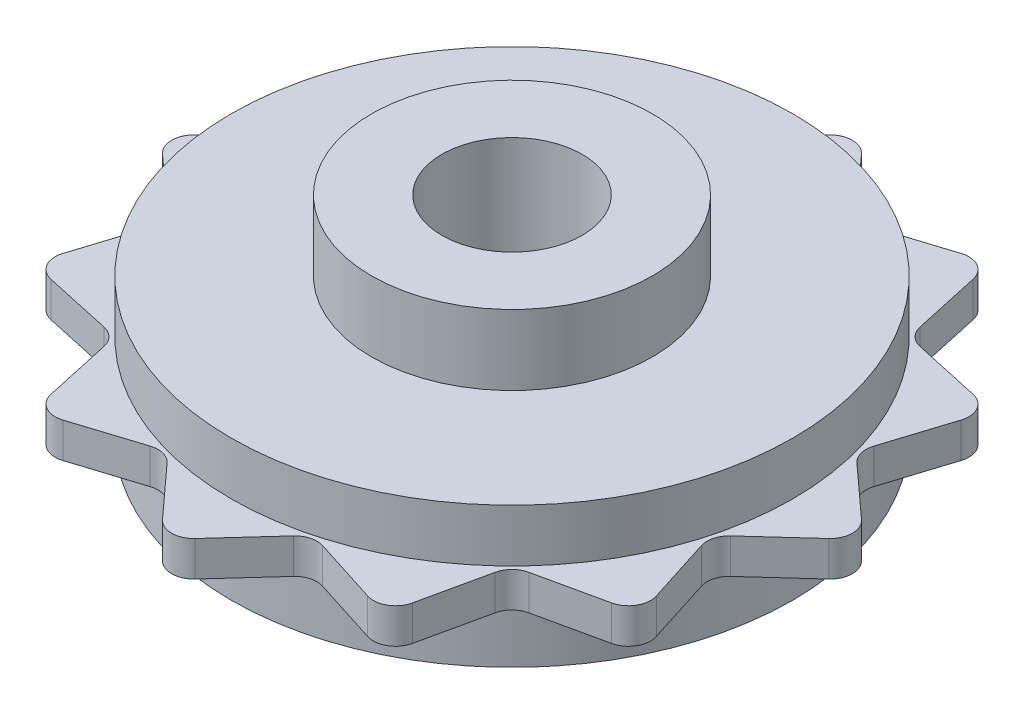
SolidWorks part; units mm, degrees
material "1023 Carbon Steel Sheet (SS)"
ref_plane "Front Plane" through (0, 0, 0) normal (0, 0, 1) x (1, 0, 0)
ref_plane "Top Plane" through (0, 0, 0) normal (0, 1, 0) x (1, 0, 0)
ref_plane "Right Plane" through (0, 0, 0) normal (1, 0, 0) x (0, 0, -1)
sketch "Sketch1" plane through (0, 0, 0) normal (0, 1, 0) x (1, 0, 0)
  circle A0 centre (0, 0) radius 6.35
  dimension "D1" = 12.7
extrude "Boss-Extrude1" add sketch "Sketch1" along normal mid plane 12.7 from surface starting at plane "Top Plane"
sketch "Sketch2" plane through (0, 0, 0) normal (0, 1, 0) x (1, 0, 0)
  circle A0 centre (0, 0) radius 12.7
  dimension "D1" = 25.4
extrude "Boss-Extrude2" add sketch "Sketch2" along normal mid plane 6.35 from surface starting at plane "Top Plane"
ref_plane "Plane1" through (0, 0, 0) normal (0, 1, 0) x (1, 0, 0)
sketch "Sketch3" plane through (0, 0, 0) normal (0, 1, 0) x (1, 0, 0)
  line L0 (0, 0) -> (0, -15.875) construction
  line L1 (0, 0) -> (-4.4774, -16.7099) construction
  line L2 (-3.287, -12.2673) -> (0, -15.875) construction
  line L3 (0, 0) -> (-9.078, -15.7235) construction
  line L4 (-3.287, -12.2673) -> (-7.9375, -13.7482) construction
  line L5 (-6.8917, -13.4151) -> (-3.8979, -12.4618)
  line L6 (-2.8552, -12.7412) -> (-0.7392, -15.0637)
  line L7 (-7.6951, -13.3283) -> (-6.35, -10.9985)
  line L8 (-6.35, -10.9985) -> (0, -12.7)
  line L9 (0, -12.7) -> (0, -15.3902)
  circle A0 centre (0, 0) radius 12.7 construction
  arc A1 (-0.7392, -15.0637) -> (0, -15.3902) centre (0, -14.3902) ccw
  circle A2 centre (0, 0) radius 15.875 construction
  arc A3 (-7.6951, -13.3283) -> (-6.8917, -13.4151) centre (-7.1951, -12.4623) ccw
  arc A4 (-3.8979, -12.4618) -> (-2.8552, -12.7412) centre (-3.5944, -13.4146) cw
  point P14 (-0.7392, -15.0637)
  dimension "D3" = 1
  dimension "D2" = 3.175
  dimension "D5" = 1
  dimension "D6" = 1
  dimension "D1" = 15
  dimension "D4" = 15
extrude "Boss-Extrude3" add sketch "Sketch3" along normal mid plane 1.5875
pattern_circular "CirPattern1" count 12 over 360 about axis through (0, 3.175, 0) along (0, -1, 0) of "Boss-Extrude3"
sketch "Sketch4" plane through (0, 6.35, 0) normal (0, 1, 0) x (1, 0, 0)
  circle A0 centre (0, 0) radius 3.175
  dimension "D1" = 6.35
extrude "Cut-Extrude1" cut sketch "Sketch4" against normal through all
